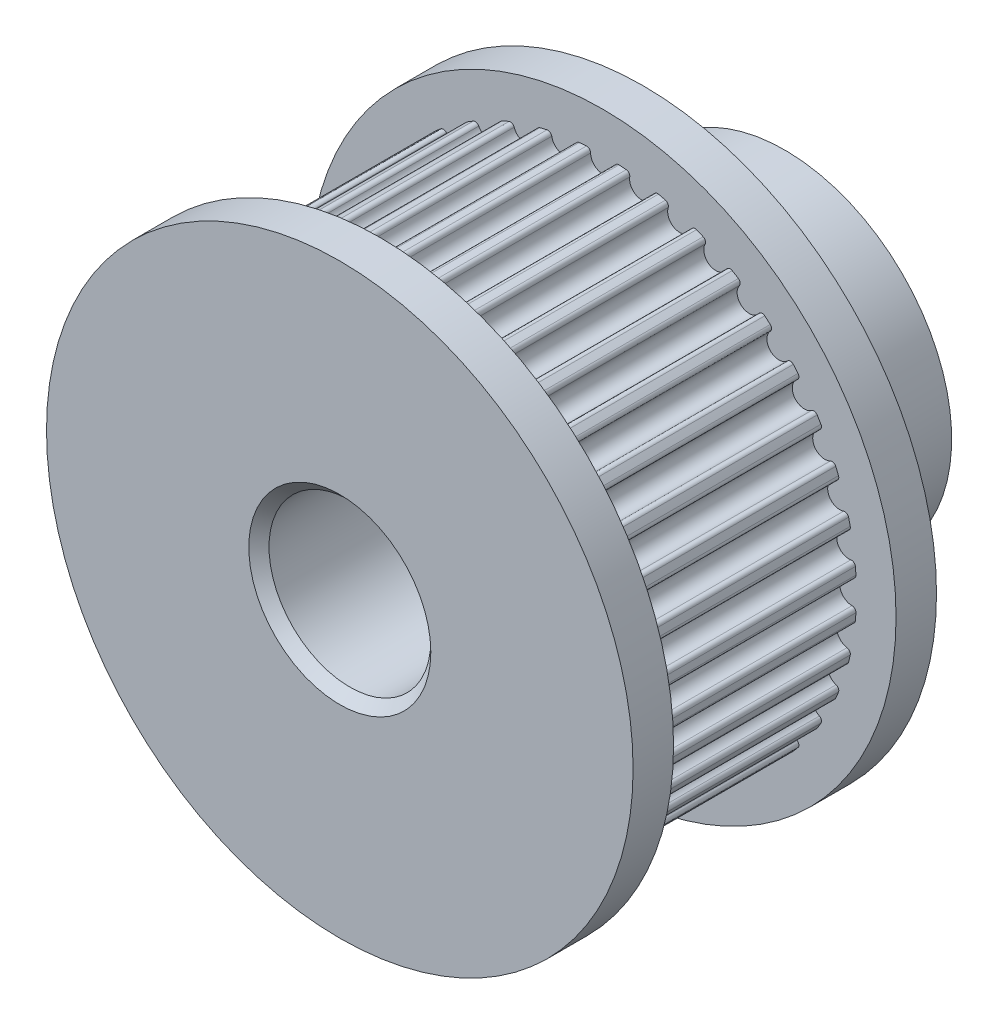
SolidWorks part; units mm, degrees
ref_plane "Спереди" through (0, 0, 0) normal (0, 0, 1) x (1, 0, 0)
ref_plane "Сверху" through (0, 0, 0) normal (0, 1, 0) x (1, 0, 0)
ref_plane "Справа" through (0, 0, 0) normal (1, 0, 0) x (0, 0, -1)
ref_axis "Ось1" through (0, 0, 55) along (0, 0, -1)
sketch "SketchRevolveGearBelt02" plane through (0, 0, 0) normal (1, 0, 0) x (0, 0, -1)
  line L1 (5.5, 0) -> (5.5, 12.5419)
  line L2 (5.5, 12.5419) -> (-5.5, 12.5419)
  line L3 (-5.5, 12.5419) -> (-5.5, 0)
  line L4 (-5.5, 0) -> (5.5, 0)
  dimension "D1" = 5.5
  dimension "D2" = 11
  dimension "D3" = 12.5419
revolve "GearBelt02" add sketch "SketchRevolveGearBelt02" angle 360 about L4 region at (0, 6.2709, 0)
sketch "SketchToothGearBelt02" plane through (0, 0, 0) normal (0, 0, 1) x (1, 0, 0)
  line L0 (-0.8059, 12.516) -> (0, 15.0819)
  line L1 (0, 15.0819) -> (0.8059, 12.516)
  arc A0 (0.8059, 12.516) -> (0.6, 12.3229) centre (0.7935, 12.3229) ccw
  arc A1 (0.6, 12.3229) -> (-0.6, 12.3229) centre (0, 12.3229) cw
  arc A2 (-0.6, 12.3229) -> (-0.8059, 12.516) centre (-0.7935, 12.3229) ccw
  dimension "GearBeltToothR1" = 0.387
  dimension "GearBeltToothR2" = 1.2
  dimension "GearBeltToothCapX1" = 0.8059
  dimension "GearBeltToothCapY1" = 2.5659
  dimension "GearBeltToothCapX2" = 0.8059
  dimension "GearBeltToothCapY2" = 2.5659
extrude "ToothExtrudeCutGearBelt02" cut sketch "SketchToothGearBelt02" against normal blind 5.5 and the other way blind 5.5
ref_axis "Ось2" through (13.7961, 0, 0) along (-1, 0, 0)
ref_plane "Плоскость1" through (0, 0, 0) normal (0, 0, -1) x (1, 0, 0)
pattern_circular "PatternGearBelt02" count 40 every 9 about axis through (0, 0, 55) along (0, 0, -1) of "ToothExtrudeCutGearBelt02"
sketch "Эскиз5" plane through (0, 0, 5.5) normal (0, 0, 1) x (1, 0, 0)
  circle A0 centre (0, 0) radius 14.5
  dimension "D1" = 29
extrude "Бобышка-Вытянуть1" add sketch "Эскиз5" along normal blind 2
sketch "Эскиз6" plane through (0, 0, -5.5) normal (0, 0, -1) x (-1, 0, 0)
  circle A0 centre (0, 0) radius 14.5
extrude "Бобышка-Вытянуть2" add sketch "Эскиз6" along normal blind 2
sketch "Эскиз7" plane through (0, 0, -7.5) normal (0, 0, -1) x (-1, 0, 0)
  circle A0 centre (0, 0) radius 8.25
extrude "Бобышка-Вытянуть3" add sketch "Эскиз7" along normal blind 7
sketch "Эскиз8" plane through (0, 0, 0) normal (0, 0, 1) x (1, 0, 0)
  circle A0 centre (0, 0) radius 4
extrude "Вырез-Вытянуть2" cut sketch "Эскиз8" against normal through all both and the other way through all
chamfer "Фаска1" distance 0.5 angle 45 2 edges at (4, 0, 7.5) (4, 0, -14.5)
